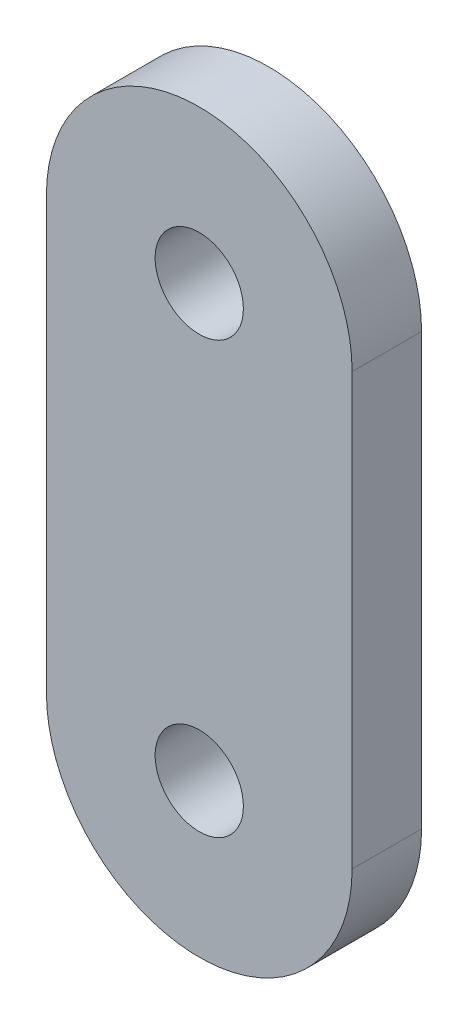
SolidWorks part; units mm, degrees
material "Plain Carbon Steel"
ref_plane "Front Plane" through (0, 0, 0) normal (0, 0, 1) x (1, 0, 0)
ref_plane "Top Plane" through (0, 0, 0) normal (0, 1, 0) x (1, 0, 0)
ref_plane "Right Plane" through (0, 0, 0) normal (1, 0, 0) x (0, 0, -1)
sketch "Sketch1" plane through (0, 0, 0) normal (0, 0, 1) x (1, 0, 0)
  line L0 (11, 0) -> (11, 31)
  line L1 (-11, 31) -> (-11, 0)
  arc A0 (-11, 0) -> (11, 0) centre (0, 0) ccw
  arc A1 (11, 31) -> (-11, 31) centre (0, 31) ccw
  circle A2 centre (0, 0) radius 3.175
  circle A3 centre (0, 31) radius 3.175
  dimension "D1" = 6.35
  dimension "D3" = 6.35
  dimension "D4" = 11
  dimension "D6" = 11
  dimension "D2" = 31
  dimension "D5" = 31
extrude "Boss-Extrude1" add sketch "Sketch1" along normal blind 5
